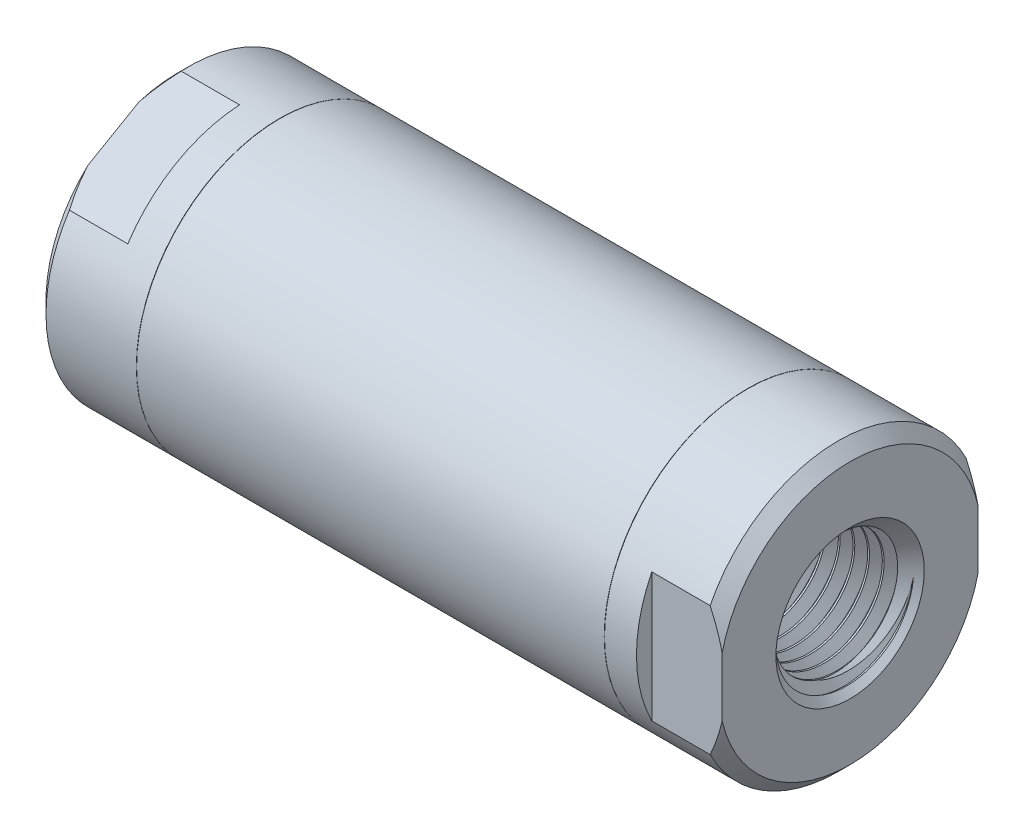
SolidWorks part; units mm, degrees
ref_plane "Front Plane" through (0, 0, 0) normal (0, 0, 1) x (1, 0, 0)
ref_plane "Top Plane" through (0, 0, 0) normal (0, 1, 0) x (1, 0, 0)
ref_plane "Right Plane" through (0, 0, 0) normal (1, 0, 0) x (0, 0, -1)
sketch "Sketch1" plane through (0, 0, 0) normal (0, 0, 1) x (1, 0, 0)
  line L0 (-33.401, 0) -> (33.401, 0) construction
  line L1 (33.401, -14.224) -> (33.401, 14.224) construction
  line L2 (33.401, 5.5562) -> (23.1953, 5.5562) construction
  line L3 (23.1953, -5.5563) -> (23.1953, 5.5562) construction
  line L6 (28.2981, -6.858) -> (28.2981, 6.858) construction
  line L7 (0, -14.224) -> (0, 14.224) construction
  point P4 (0, 0)
  point P8 (33.401, 0)
  point P10 (28.2981, 5.5562)
  point P13 (23.1953, 0)
  point P22 (28.2981, 0)
  point P25 (0, 0)
sketch "Sketch3" plane through (0, 0, 0) normal (0, 0, 1) x (1, 0, 0)
  line L0 (33.401, 5.5562) -> (33.401, 14.224)
  line L1 (33.401, 14.224) -> (23.241, 14.224)
  line L2 (-33.401, 14.224) -> (-33.401, 5.5562)
  line L3 (-33.401, 5.5562) -> (-21.6078, 5.5562)
  line L5 (33.401, 5.5562) -> (21.6078, 5.5562)
  line L9 (-33.401, 0) -> (33.401, 0) construction
  line L11 (10.7791, 11.049) -> (-12.8765, 11.049)
  line L12 (16.8453, 11.049) -> (11.176, 11.049)
  line L14 (10.7791, 11.049) -> (10.7791, 0)
  line L15 (10.7791, 0) -> (11.176, 0)
  line L16 (11.176, 11.049) -> (11.176, 0)
  line L17 (-21.6078, 5.5562) -> (-21.6078, 5.1594)
  line L18 (-21.6078, 5.1594) -> (-16.8453, 5.1594)
  line L20 (-12.8765, 11.049) -> (-12.8765, 11.4459)
  line L21 (-12.8765, 11.4459) -> (-16.8453, 11.4459)
  line L22 (-16.8453, 11.4459) -> (-16.8453, 5.1594)
  line L23 (21.6078, 5.5562) -> (21.6078, 5.1594)
  line L24 (21.6078, 5.1594) -> (16.8453, 5.1594)
  line L25 (16.8453, 5.1594) -> (16.8453, 11.049)
  line L26 (23.2156, 14.224) -> (-23.2156, 14.224)
  line L28 (-23.241, 14.224) -> (-23.241, 13.589)
  line L29 (-23.241, 13.589) -> (-23.2156, 13.589)
  line L30 (-23.2156, 14.224) -> (-23.2156, 13.589)
  line L32 (23.2156, 14.224) -> (23.2156, 13.589)
  line L33 (23.2156, 13.589) -> (23.241, 13.589)
  line L34 (23.241, 14.224) -> (23.241, 13.589)
  line L35 (-23.241, 14.224) -> (-33.401, 14.224)
  dimension "D1" = 3.175
  dimension "D4" = 11.7932
  dimension "D5" = 3.9688
  dimension "D6" = 0.3969
  dimension "D7" = 4.7625
  dimension "D8" = 11.7932
  dimension "D9" = 0.0254
  dimension "D10" = 0.635
  dimension "D11" = 10.16
  dimension "D12" = 0.0254
  dimension "D13" = 0.635
  dimension "D2" = 0.3969
revolve "Revolve1" add sketch "Sketch3" angle 360 about L0
chamfer "Chamfer1" distance 1.1906 angle 45 2 edges at (33.401, 0, 14.224) (-33.401, 0, 14.224)
chamfer "Chamfer2" distance 0.7937 angle 45 2 edges at (-16.8453, 0, 5.1594) (16.8453, 0, 5.1594)
sketch "Sketch4" plane through (33.401, 0, 0) normal (1, 0, 0) x (0, 0, -1)
  line L0 (-12.7, 6.4056) -> (-12.7, -6.4056)
  line L1 (12.7, 6.4056) -> (12.7, -6.4056)
  line L2 (-12.7, 0) -> (12.7, 0) construction
  circle A0 centre (0, 0) radius 14.224 construction
  arc A1 (12.7, -6.4056) -> (12.7, 6.4056) centre (0, 0) ccw
  arc A3 (-12.7, 6.4056) -> (-12.7, -6.4056) centre (0, 0) ccw
  point P8 (0, 0)
extrude "Cut-Extrude1" cut sketch "Sketch4" against normal blind 6.985
sketch "Sketch5" plane through (-33.401, 0, 0) normal (-1, 0, 0) x (0, 0, 1)
  line L0 (0.8026, 14.2013) -> (11.8974, 7.7957)
  line L1 (-11.8974, -7.7957) -> (-0.8026, -14.2013)
  line L2 (0, -14.224) -> (0, 14.224) construction
  line L3 (-6.35, -10.9985) -> (6.35, 10.9985) construction
  arc A1 (11.8974, 7.7957) -> (0.8026, 14.2013) centre (0, 0) ccw
  circle A2 centre (0, 0) radius 14.224 construction
  arc A3 (-11.8974, -7.7957) -> (-0.8026, -14.2013) centre (0, 0) ccw
  point P10 (0, 0)
  dimension "D1" = 60
  dimension "D2" = 25.4
extrude "Cut-Extrude2" cut sketch "Sketch5" against normal blind 6.985
sketch "Sketch6" plane through (11.176, 0, 0) normal (1, 0, 0) x (0, 0, -1)
  line L0 (-5.5562, -9.5503) -> (5.5562, -9.5503) construction
  line L1 (0, -11.049) -> (0, -9.5503) construction
  line L2 (-9.5503, 5.5562) -> (-9.5503, -5.5563) construction
  line L3 (-11.049, 0) -> (-9.5503, 0) construction
  line L4 (5.5562, 9.5503) -> (-5.5563, 9.5503) construction
  line L5 (0, 11.049) -> (0, 9.5503) construction
  line L6 (9.5503, -5.5563) -> (9.5503, 5.5563) construction
  line L7 (11.049, 0) -> (9.5503, 0) construction
  circle A0 centre (0, 0) radius 2.3813
  circle A1 centre (0, 0) radius 11.049 construction
  arc A2 (-5.5562, -9.5503) -> (5.5562, -9.5503) centre (0, 0) ccw
  arc A3 (-5.5562, -9.5503) -> (5.5562, -9.5503) centre (0, -11.049) cw
  arc A4 (-9.5503, 5.5562) -> (-9.5503, -5.5563) centre (-11.049, 0) cw
  arc A5 (-9.5503, 5.5562) -> (-9.5503, -5.5563) centre (0, 0) ccw
  arc A6 (5.5562, 9.5503) -> (-5.5563, 9.5503) centre (0, 11.049) cw
  arc A7 (5.5562, 9.5503) -> (-5.5563, 9.5503) centre (0, 0) ccw
  arc A8 (9.5503, -5.5563) -> (9.5503, 5.5563) centre (11.049, 0) cw
  arc A9 (9.5503, -5.5563) -> (9.5503, 5.5563) centre (0, 0) ccw
  point P22 (0, 0)
  dimension "D1" = 4.7625
  dimension "D2" = 11.1125
  dimension "D3" = 4
extrude "Cut-Extrude3" cut sketch "Sketch6" against normal up to next
sketch "Sketch7" plane through (0, 0, 0) normal (0, 0, 1) x (1, 0, 0)
  line L0 (-4.0606, 0) -> (-18.3481, 0)
  line L1 (-33.401, 0) -> (33.401, 0) construction
  line L2 (-4.0606, 0) -> (-4.0606, 1.5875)
  line L3 (-4.0606, 1.5875) -> (-10.4106, 1.5875)
  line L4 (-10.4106, 1.5875) -> (-10.4106, 9.4615)
  line L5 (10.7791, 11.049) -> (-12.8765, 11.049) construction
  arc A0 (-18.3481, 0) -> (-10.4106, 9.4615) centre (-8.7403, 0) cw
  dimension "D3" = 1.5875
  dimension "D1" = 1.5875
  dimension "D2" = 6.35
  dimension "D4" = 7.9375
revolve "Revolve2" add sketch "Sketch7" angle 360 about L0
sketch "Sketch13" plane through (-33.401, 0, 0) normal (-1, 0, 0) x (0, 0, 1)
  circle A0 centre (0, 0) radius 6.858 construction
  point P3 (0, -6.858)
sketch "Sketch2" plane through (0, 0, 0) normal (1, 0, 0) x (0, 0, -1)
  circle A0 centre (0, 0) radius 14.224 construction
sketch "Sketch8" plane through (0, 0, 0) normal (0, 0, 1) x (1, 0, 0)
  line L0 (33.401, 0) -> (33.401, 6.858)
  line L1 (33.401, -14.224) -> (33.401, 14.224) construction
  line L2 (33.401, 6.858) -> (23.1953, 6.5402)
  line L3 (23.1953, 6.5402) -> (23.1953, 0)
  line L4 (23.1953, 0) -> (33.401, 0)
  dimension "D1" = 1.783
revolve "Revolve3" add sketch "Sketch8" angle 360 about L4
sketch "Sketch9" plane through (33.401, 0, 0) normal (1, 0, 0) x (0, 0, -1)
  circle A1 centre (0, 0) radius 6.858
  circle A2 centre (0, 0) radius 6.858
  dimension "D1" = 0
curve "Helix/Spiral1" parameters "Pitch"=1.4111
sketch "Sketch10" plane through (0, 0, 0) normal (0, 0, 1) x (1, 0, 0)
  line L0 (33.401, 6.858) -> (33.9302, 5.9415) construction
  line L1 (33.9302, 5.9415) -> (34.1066, 5.9415) construction
  line L2 (34.1066, 5.9415) -> (34.6357, 6.858) construction
  line L3 (34.6357, 6.858) -> (33.401, 6.858) construction
  line L4 (33.6656, 6.3997) -> (34.3711, 6.3997) construction
  line L5 (34.0184, 6.858) -> (34.0184, 5.9415) construction
  line L6 (33.9302, 5.9415) -> (32.8718, 7.7745)
  line L7 (34.1066, 5.9415) -> (35.1649, 7.7745)
  line L8 (35.1649, 7.7745) -> (32.8718, 7.7745)
  line L9 (33.9302, 5.9415) -> (34.1066, 5.9415)
  line L10 (33.401, -6.858) -> (33.401, 6.858) construction
  line L11 (33.401, 6.858) -> (23.1953, 6.5402) construction
  dimension "D1" = 60
  dimension "D2" = 0.1764
  dimension "D3" = 0.7056
sweep "Cut-Sweep1" cut profiles "Sketch10" path "Helix/Spiral1"
pattern_circular "CirPattern1" count 2 over 360 about axis through (0, -14.224, 0) along (0, 1, 0) of bodies 115
combine bodies "Combine1" operation type subtract main body 122 bodies to subtract 116 115
sketch "Sketch11" plane through (33.401, 0, 0) normal (1, 0, 0) x (0, 0, -1)
  circle A0 centre (0, 0) radius 7.366
  dimension "D1" = 14.732
extrude "Cut-Extrude4" cut sketch "Sketch11" against normal through all draft 45
sketch "Sketch12" plane through (-33.401, 0, 0) normal (-1, 0, 0) x (0, 0, 1)
  circle A0 centre (0, 0) radius 7.366
  dimension "D1" = 14.732
extrude "Cut-Extrude5" cut sketch "Sketch12" against normal through all draft 45
equation "\"D3@Helix/Spiral1\" = \"Thread Engagement (L2)@Sketch1\" + \"Pitch@Helix/Spiral1\""
equation "\"D2@Sketch10\" = \"Pitch@Helix/Spiral1\" * .125"
equation "\"D3@Sketch10\" = \"Pitch@Helix/Spiral1\" * .5"
equation "\"D1@Sketch11\" = \"Thread OD@Sketch1\" + .04"
equation "\"D1@Sketch12\" = \"D1@Sketch11\""
equation "\"D4@Sketch3\" = \"Thread Engagement (L2)@Sketch1\" + .0625"
equation "\"D8@Sketch3\" = \"D4@Sketch3\""
equation "\"D11@Sketch3\" = \"End Length@Sketch3\""
equation "\"D2@Sketch5\"=\"Across Flat Length@Sketch4\""
equation "\"D1@Cut-Extrude1\"=\"D11@Sketch3\"-.125"
equation "\"D1@Cut-Extrude2\"=\"D1@Cut-Extrude1\""
